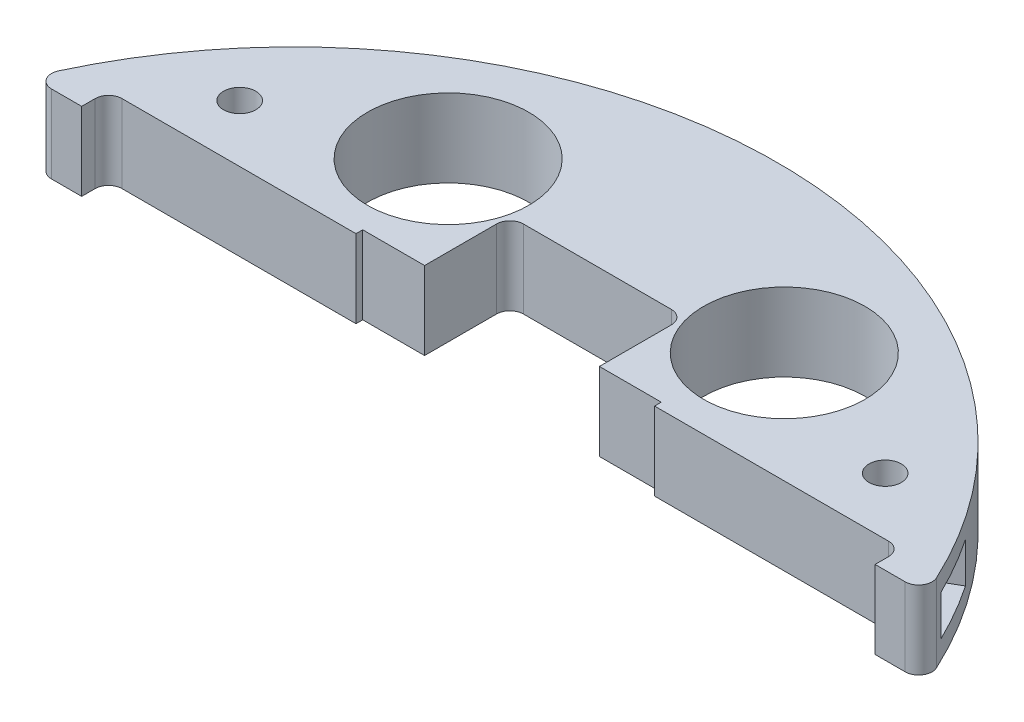
SolidWorks part; units mm, degrees
material "ABS"
ref_plane "Front Plane" through (0, 0, 0) normal (0, 0, 1) x (1, 0, 0)
ref_plane "Top Plane" through (0, 0, 0) normal (0, 1, 0) x (1, 0, 0)
ref_plane "Right Plane" through (0, 0, 0) normal (1, 0, 0) x (0, 0, -1)
sketch "Sketch1" plane through (0, 0, 0) normal (0, 1, 0) x (1, 0, 0)
  line L0 (0, -85) -> (-32.2211, -64.3879) construction
  line L1 (0, -85) -> (0, 0) construction
  arc A0 (36.2245, -62.2237) -> (-36.2245, -62.2237) centre (0, 0) ccw
  arc A1 (29.8119, -61.0352) -> (-29.8119, -61.0352) centre (0, -85) ccw
  arc A2 (36.2245, -62.2237) -> (29.8119, -61.0352) centre (33.7089, -57.9026) cw
  arc A3 (-29.8119, -61.0352) -> (-36.2245, -62.2237) centre (-33.7089, -57.9026) cw
  dimension "D1" = 144
  dimension "D2" = 76.5
  dimension "D4" = 5
  dimension "D3" = 85
extrude "Boss-Extrude1" add sketch "Sketch1" along normal mid plane 11.6
sketch "solenoid placement" plane through (0, 5.8, 0) normal (0, 1, 0) x (1, 0, 0)
  line L0 (0, 0) -> (0, -36) construction
  line L5 (-19, -36) -> (19, -36)
  line L7 (19, -36) -> (19, 28)
  line L9 (19, 28) -> (-19, 28)
  line L11 (-19, 28) -> (-19, -36)
  circle A1 centre (0, 0) radius 72 construction
  arc A2 (36.2245, -62.2237) -> (-36.2245, -62.2237) centre (0, 0) ccw construction
  dimension "D1" = 36
  dimension "D2" = 64
  dimension "D3" = 38
extrude "Cut-Extrude1" cut sketch "solenoid placement" against normal through all
sketch "Sketch4" plane through (0, 5.8, 0) normal (0, 1, 0) x (1, 0, 0)
  line L1 (-13, 28) -> (13, 28)
  line L2 (-13, 28) -> (-13, 43.2)
  line L4 (13, 28) -> (13, 43.2)
  line L5 (11, 45.2) -> (-11, 45.2)
  line L6 (19, 28) -> (-19, 28) construction
  arc A0 (11, 45.2) -> (13, 43.2) centre (11, 43.2) cw
  arc A1 (-11, 45.2) -> (-13, 43.2) centre (-11, 43.2) ccw
  point P6 (0, 28)
  dimension "D1" = 2
  dimension "D2" = 26
  dimension "D3" = 17.2
extrude "Cut-Extrude4" cut sketch "Sketch4" against normal through all
sketch "Sketch5" plane through (0, 5.8, 0) normal (0, 1, 0) x (1, 0, 0)
  line L0 (0, 0) -> (0, 72) construction
  arc A0 (36.2245, -62.2237) -> (-36.2245, -62.2237) centre (0, 0) ccw construction
  circle A1 centre (25, 48) radius 12
  circle A3 centre (-25, 48) radius 12
  dimension "D3" = 24
  dimension "D1" = 25
  dimension "D2" = 48
extrude "Cut-Extrude5" cut sketch "Sketch5" against normal through all
sketch "Sketch6" plane through (0, 5.8, 0) normal (0, 1, 0) x (1, 0, 0)
  line L0 (0, 0) -> (0, 72) construction
  arc A0 (36.2245, -62.2237) -> (-36.2245, -62.2237) centre (0, 0) ccw construction
  circle A1 centre (48, 40) radius 2.4
  circle A6 centre (-48, 40) radius 2.4
  dimension "D3" = 4.8
  dimension "D1" = 48
  dimension "D2" = 40
extrude "Cut-Extrude6" cut sketch "Sketch6" against normal through all
sketch "Sketch3" plane through (0, 5.8, 0) normal (0, 1, 0) x (1, 0, 0)
  line L0 (-19, 28) -> (19, 28)
  line L1 (-72, -31.5) -> (72, -31.5) construction
  line L2 (-72, -31.5) -> (-72, 27.5)
  line L3 (-59, 31.5) -> (-19, 31.5)
  line L4 (72, -31.5) -> (72, 27.5)
  line L5 (0, -31.5) -> (0, 31.5) construction
  line L6 (72, 27.5) -> (59, 27.5)
  line L7 (19, 28) -> (19, 31.5)
  line L8 (-19, 28) -> (-19, 31.5)
  line L9 (19, 31.5) -> (59, 31.5)
  line L10 (-72, -31.5) -> (-72, -101.6464)
  line L11 (72, -31.5) -> (72, -101.6464)
  line L12 (72, -101.6464) -> (-72, -101.6464)
  line L13 (59, 27.5) -> (59, 31.5)
  line L14 (-59, 27.5) -> (-59, 31.5)
  line L15 (-72, 27.5) -> (-59, 27.5)
  arc A0 (36.2245, -62.2237) -> (-36.2245, -62.2237) centre (0, 0) ccw construction
  point P0 (0, 0)
  dimension "D2" = 13
  dimension "D1" = 63
  dimension "D3" = 4
extrude "Cut-Extrude3" cut sketch "Sketch3" against normal through all
sketch "Sketch7" plane through (0, 0, 0) normal (0, 1, 0) x (1, 0, 0)
  line L0 (0, 0) -> (62.3538, 36) construction
  line L1 (0, 0) -> (-62.3538, 36) construction
  line L2 (0, 0) -> (0, 72) construction
  arc A0 (0, 72) -> (62.3538, 36) centre (0, 0) cw construction
  arc A1 (0, 72) -> (-62.3538, 36) centre (0, 0) ccw construction
  arc A2 (66.5413, 27.5) -> (-66.5413, 27.5) centre (0, 0) ccw construction
  dimension "D1" = 120
fillet "Fillet1" radius 2 4 edges at (-66.5413, 0, -27.5) (-59, 0, -31.5) (59, 0, -31.5) (66.5413, 0, -27.5)
sketch "Sketch8" plane through (0, 0, 0) normal (0, 1, 0) x (1, 0, 0)
  line L0 (5, 71.8262) -> (5, 68.9262)
  line L1 (0, 0) -> (64.7033, 31.583) construction
  line L2 (64.7033, 31.583) -> (59.7033, 40.2432) construction
  line L3 (64.7033, 31.583) -> (62.1918, 30.133)
  line L4 (62.1918, 30.133) -> (57.1918, 38.7932)
  line L5 (59.7033, 40.2432) -> (57.1918, 38.7932)
  line L6 (0, 0) -> (59.7033, 40.2432) construction
  line L7 (5, 68.9262) -> (-5, 68.9262)
  line L8 (-5, 71.8262) -> (-5, 68.9262)
  line L9 (5, 71.8262) -> (-5, 71.8262) construction
  line L10 (-59.7033, 40.2432) -> (-57.1918, 38.7932)
  line L11 (-57.1918, 38.7932) -> (-62.1918, 30.133)
  line L12 (-64.7033, 31.583) -> (-62.1918, 30.133)
  line L13 (-59.7033, 40.2432) -> (-64.7033, 31.583) construction
  arc A0 (59.7033, 40.2432) -> (64.7033, 31.583) centre (0, 0) cw
  arc A2 (-5, 71.8262) -> (5, 71.8262) centre (0, 0) cw
  arc A3 (-64.7033, 31.583) -> (-59.7033, 40.2432) centre (0, 0) cw
  point P4 (62.3538, 36)
  point P10 (-62.3538, 36)
  point P18 (0, 0)
  dimension "D1" = 10
  dimension "D2" = 2.9
extrude "Cut-Extrude7" cut sketch "Sketch8" against normal mid plane 6
sketch "Sketch9" plane through (0, 5.8, 0) normal (0, 1, 0) x (1, 0, 0)
  line L1 (22.2, -32.5) -> (-22.2, -32.5)
  line L2 (22.2, -32.5) -> (22.2, 32.5)
  line L3 (22.2, 32.5) -> (-22.2, 32.5)
  line L4 (-22.2, -32.5) -> (-22.2, 32.5)
  line L5 (22.2, -32.5) -> (-22.2, 32.5) construction
  line L6 (22.2, 32.5) -> (-22.2, -32.5) construction
  point P0 (0, 0)
  dimension "D1" = 44.4
  dimension "D2" = 65
extrude "Cut-Extrude8" cut sketch "Sketch9" against normal through all
equation "\"smallPulleyTeeth\"= 15"
equation "\"largePulleyTeeth\"= 30"
equation "\"eighthThick\"= 2.9mm"
equation "\"sixteenthThick\" = 1.7mm"
equation "\"quarterThick\"=6.0mm"
equation "\"OD\" = 145mm"
equation "\"puckAngle\" = 60.5deg"
equation "\"puckDiam\" = 76.5mm"
equation "\"D2@Sketch1\"=\"puckDiam\""
equation "\"D1@Boss-Extrude1\"=\"eighthThick\"*4"
equation "\"axlePress\" = 5.9mm"
equation "\"press\" = 0.2mm"
equation "\"wheelClear\" = 0.3mm"
equation "\"10-32clear\" = 4.8mm"
equation "\"6-32clear\" = 3.3mm"
equation "\"8-32clear\" = 4.0mm"
equation "\"wheelHeight\" = 22mm"
equation "\"wheelWell\" = 65mm"
equation "\"puckDist\" = 85mm"
equation "\"scoopFillet\" = 5mm"
equation "\"4-40clear\" = 3.0mm"
equation "\"D3@Sketch1\"=\"puckDist\""
equation "\"D4@Sketch1\"=\"scoopFillet\""
equation "\"D3@Sketch6\"=\"10-32clear\""
equation "\"D2@Sketch8\"=\"eighthThick\""
equation "\"D2@Sketch9\"=\"wheelWell\""
